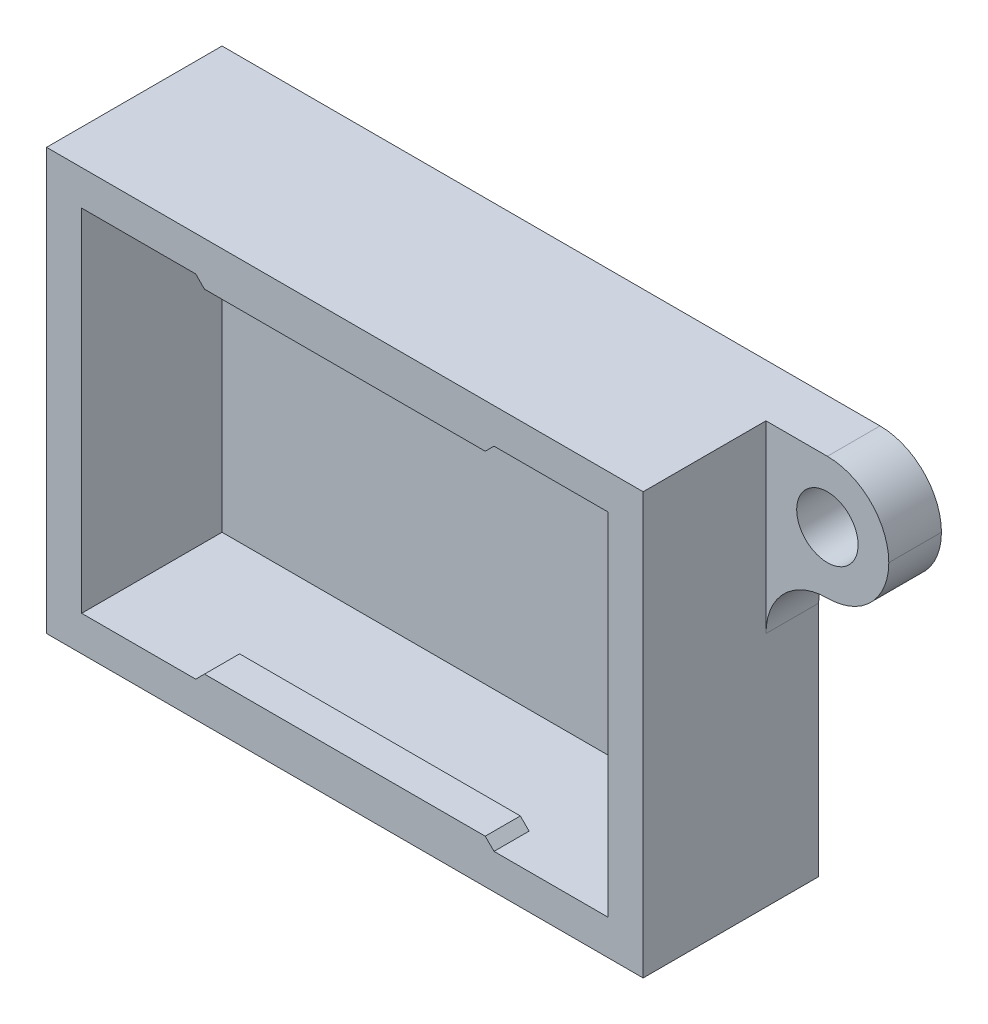
SolidWorks part; units mm, degrees
material "ABS-White"
ref_plane "Front Plane" through (0, 0, 0) normal (0, 0, 1) x (1, 0, 0)
ref_plane "Top Plane" through (0, 0, 0) normal (0, 1, 0) x (1, 0, 0)
ref_plane "Right Plane" through (0, 0, 0) normal (1, 0, 0) x (0, 0, -1)
sketch "Sketch1" plane through (0, 0, 0) normal (0, 0, 1) x (1, 0, 0)
  line L1 (-17, -12) -> (17, -12)
  line L2 (-17, -12) -> (-17, 12)
  line L3 (-17, 12) -> (17, 12)
  line L4 (17, -12) -> (17, 12)
  line L5 (-17, -12) -> (17, 12) construction
  line L6 (-17, 12) -> (17, -12) construction
  point P0 (0, 0)
  dimension "D1" = 24
  dimension "D2" = 34
extrude "Boss-Extrude1" add sketch "Sketch1" along normal blind 10
sketch "Sketch2" plane through (0, 0, 10) normal (0, 0, 1) x (1, 0, 0)
  line L1 (-15, -10) -> (15, -10)
  line L2 (-15, -10) -> (-15, 10)
  line L3 (-15, 10) -> (15, 10)
  line L4 (15, -10) -> (15, 10)
  line L5 (-15, -10) -> (15, 10) construction
  line L6 (-15, 10) -> (15, -10) construction
  point P0 (0, 0)
  dimension "D1" = 30
  dimension "D2" = 20
extrude "Cut-Extrude1" cut sketch "Sketch2" against normal blind 8
sketch "Sketch3" plane through (0, 10, 0) normal (0, -1, 0) x (1, 0, 0)
  line L0 (15, 10) -> (-15, 10) construction
  line L1 (-8, 10) -> (8, 10)
  line L2 (-8, 10) -> (-8, 8)
  line L3 (-8, 8) -> (8, 8)
  line L4 (8, 10) -> (8, 8)
  line L5 (-15, 2) -> (-15, 10) construction
  line L6 (15, 2) -> (15, 10) construction
  dimension "D1" = 7
  dimension "D2" = 7
  dimension "D3" = 2
extrude "Boss-Extrude2" add sketch "Sketch3" along normal blind 0.5
mirror "Mirror1" about plane through (0, 0, 0) normal (0, 1, 0) of "Boss-Extrude2"
chamfer "Chamfer1" distance 0.5 angle 45 4 edges at (8, 10, 9) (-8, 10, 9) (-8, -10, 9) (8, -10, 9)
sketch "Sketch4" plane through (0, 0, 0) normal (0, 0, 1) x (1, 0, 0)
  line L1 (17, 12) -> (24, 12)
  line L2 (17, 12) -> (17, 5)
  line L3 (17, 5) -> (24, 5)
  line L4 (24, 12) -> (24, 5)
  dimension "D1" = 7
  dimension "D2" = 7
extrude "Boss-Extrude3" add sketch "Sketch4" along normal blind 3
fillet "Fillet1" radius 3.5 2 edges at (24, 12, 1.5) (24, 5, 1.5)
sketch "Sketch6" plane through (0, 0, 0) normal (0, 0, -1) x (-1, 0, 0)
  line L0 (-17, -12) -> (-17, 5) construction
  line L2 (-20.5, 12) -> (17, 12) construction
  circle A0 centre (-20.5, 8.5) radius 1.75
  point P6 (-15.7694, 12)
  dimension "D3" = 3.5
  dimension "D1" = 3.5
  dimension "D2" = 3.5
extrude "Cut-Extrude2" cut sketch "Sketch6" against normal through all
ref_axis "Axis1" through (0, 0, -0.5) along (0, 0, 1)
pattern_circular "CirPattern2" count 2 over 360 about axis through (0, 0, -0.5) along (0, 0, 1) of "Boss-Extrude3", "Cut-Extrude2", "Fillet1"
fillet "Fillet2" radius 3.5 2 edges
